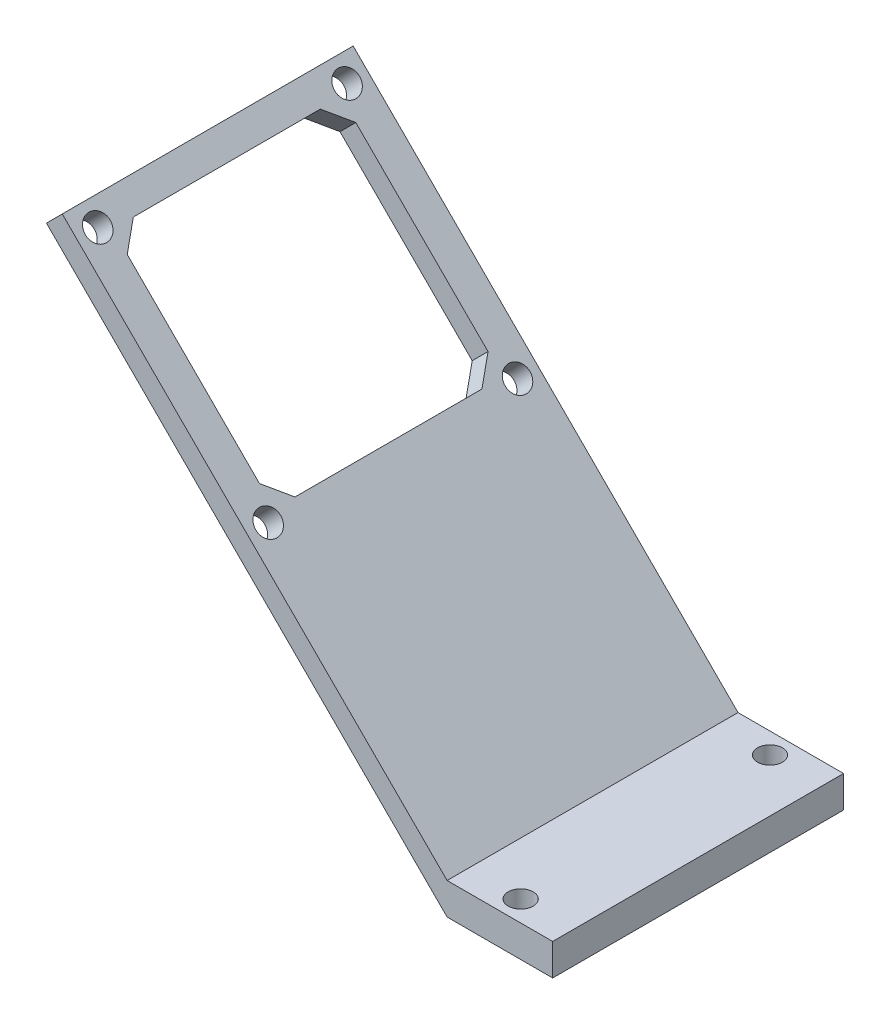
SolidWorks part; units mm, degrees
ref_plane "Front Plane" through (0, 0, 0) normal (0, 0, 1) x (1, 0, 0)
ref_plane "Top Plane" through (0, 0, 0) normal (0, 1, 0) x (1, 0, 0)
ref_plane "Right Plane" through (0, 0, 0) normal (1, 0, 0) x (0, 0, -1)
sketch "Sketch2" plane through (0, 0, 0) normal (0, 0, 1) x (1, 0, 0)
  line L0 (-23.4576, 19.6476) -> (0, -3.81)
  line L1 (12.7, -3.81) -> (0, -3.81)
  line L2 (12.7, -3.81) -> (12.7, 0)
  line L3 (12.7, 0) -> (0, 0)
  line L4 (0, -3.81) -> (0, 0)
  line L5 (-23.4576, 19.6476) -> (-21.5526, 21.5526)
  line L6 (-21.5526, 21.5526) -> (0, 0)
  line L7 (-23.4576, 19.6476) -> (-21.5526, 21.5526)
  line L8 (-23.4576, 19.6476) -> (-48.2064, 44.3964)
  line L9 (-21.5526, 21.5526) -> (-46.3014, 46.3014)
  line L10 (-48.2064, 44.3964) -> (-46.3014, 46.3014)
  dimension "D1" = 45
  dimension "D2" = 3.81
  dimension "D3" = 12.7
  dimension "D4" = 30.48
  dimension "D5" = 35
extrude "Boss-Extrude1" add sketch "Sketch2" along normal blind 35 contours L10 L8 L5 L9 | L6 L5 L0 L4 | L4 L1 L2 L3 region at (-11.2593, 9.3274, 0) region at (-34.8795, 32.9745, 0) region at (6.35, -1.905, 0)
sketch "Sketch3" plane through (0, 0, 0) normal (0.7071, 0.7071, 0) x (0.7071, -0.7071, 0)
  line L0 (0, 0) -> (-65.48, 0) construction
  line L1 (-62.98, -2.5) -> (-33.98, -2.5) construction
  line L2 (-62.98, -2.5) -> (-62.98, -32.5) construction
  line L3 (-62.98, -32.5) -> (-33.98, -32.5) construction
  line L4 (-33.98, -2.5) -> (-33.98, -32.5) construction
  line L5 (-65.48, -35) -> (-65.48, 0) construction
  line L6 (-60.98, -17.5) -> (-35.98, -17.5) construction
  line L7 (-60.98, -5) -> (-35.98, -5)
  line L8 (-60.98, -5) -> (-60.98, -30)
  line L9 (-60.98, -30) -> (-35.98, -30)
  line L10 (-35.98, -5) -> (-35.98, -30)
  line L11 (-60.98, -5) -> (-35.98, -5)
  line L12 (-60.98, -5) -> (-60.98, -3.75)
  line L13 (-60.98, -3.75) -> (-35.98, -3.75)
  line L14 (-35.98, -5) -> (-35.98, -3.75)
  line L15 (-35.98, -30) -> (-35.98, -31.25)
  line L16 (-60.98, -31.25) -> (-35.98, -31.25)
  line L17 (-60.98, -30) -> (-60.98, -31.25)
  line L18 (-48.48, -5) -> (-48.48, -30) construction
  line L19 (-60.98, -5) -> (-62.23, -5)
  line L20 (-60.98, -5) -> (-60.98, -30)
  line L21 (-60.98, -30) -> (-62.23, -30)
  line L22 (-62.23, -5) -> (-62.23, -30)
  line L23 (-35.98, -5) -> (-34.73, -5)
  line L24 (-35.98, -30) -> (-34.73, -30)
  line L25 (-34.73, -5) -> (-34.73, -30)
  line L26 (-37.23, -3.75) -> (-34.73, -6.25)
  line L27 (-37.23, -31.25) -> (-34.73, -28.75)
  line L28 (-59.73, -3.75) -> (-62.23, -6.25)
  line L29 (-59.73, -31.25) -> (-62.23, -28.75)
  point P16 (-48.48, -3.75)
  point P17 (-48.48, -5)
  point P30 (-62.98, -17.5)
  point P32 (-48.48, -2.5)
  dimension "D1" = 2.5
  dimension "D2" = 29
  dimension "D3" = 2.5
  dimension "D4" = 30
  dimension "D6" = 25
  dimension "D7" = 1.25
  dimension "D8" = 25
  dimension "D9" = 1.25
extrude "Cut-Extrude1" cut sketch "Sketch3" against normal through all contours L10 L7 L8 L9 | L13 L28 L7 L26 | L29 L8 L28 L22 | L10 L27 L25 L26 | L29 L16 L27 L9 region at (-34.2805, 34.2805, 4.386) region at (-34.2805, 34.2805, 17.5) region at (-43.5536, 43.5536, 17.5) region at (-25.0075, 25.0075, 17.5) region at (-34.2805, 34.2805, 30.614)
hole_wizard "Ø3.0mm Dowel Hole1" positions "3DSketch1" profile "Sketch4" hole size "Ø3.0" standard "ANSI Metric" end condition through all
sketch3d "3DSketch1"
  point P0 (-44.5336, 44.5336, 2.5)
  point P3 (-24.0275, 24.0275, 2.5)
  point P6 (-24.0275, 24.0275, 32.5)
  point P9 (-44.5336, 44.5336, 32.5)
sketch "Sketch4" plane through (-44.5336, 44.5336, 2.5) normal (0, 0, 1) x (-0.7071, 0.7071, 0)
  line L0 (0, 0) -> (0, 36.7811)
  line L1 (0, 36.7811) -> (1.5, 36.7811)
  line L2 (1.5, 36.7811) -> (1.5, 0)
  line L5 (1.5, 0) -> (0, 0)
  line L11 (0, -6.35) -> (0, 107.95) construction
  dimension "Thru Hole Dia." = 3
  dimension "Thru Hole Depth" = 36.7811
sketch "Sketch5" plane through (0, 0, 0) normal (0, 1, 0) x (1, 0, 0)
  line L0 (12.7, -35) -> (12.7, 0) construction
  line L1 (12.7, -2.5) -> (6.35, -2.5)
  line L2 (12.7, -2.5) -> (12.7, -32.5)
  line L3 (12.7, -32.5) -> (6.35, -32.5)
  line L4 (6.35, -2.5) -> (6.35, -32.5)
  point P6 (12.7, -17.5)
  dimension "D1" = 6.35
  dimension "D2" = 30
  dimension "D3" = 17.5
hole_wizard "Ø3.0mm Dowel Hole2" positions "3DSketch2" profile "Sketch6" hole size "Ø3.0" standard "ANSI Metric" end condition through all
sketch3d "3DSketch2"
  point P0 (6.35, 0, 2.5)
  point P3 (6.35, 0, 32.5)
sketch "Sketch6" plane through (6.35, 0, 2.5) normal (1, 0, 0) x (0, 0, 1)
  line L0 (0, 0) -> (0, 3.81)
  line L1 (0, 3.81) -> (1.5, 3.81)
  line L2 (1.5, 3.81) -> (1.5, 0)
  line L5 (1.5, 0) -> (0, 0)
  line L11 (0, -6.35) -> (0, 107.95) construction
  dimension "Thru Hole Dia." = 3
  dimension "Thru Hole Depth" = 3.81
